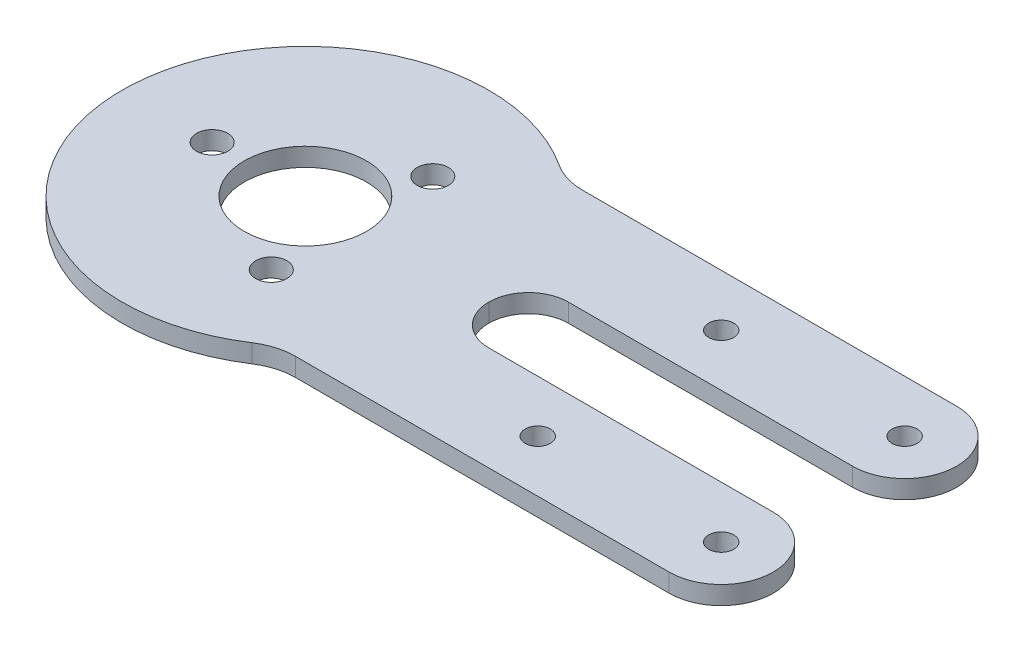
SolidWorks part; units mm, degrees
ref_plane "Front Plane" through (0, 0, 0) normal (0, 0, 1) x (1, 0, 0)
ref_plane "Top Plane" through (0, 0, 0) normal (0, 1, 0) x (1, 0, 0)
ref_plane "Right Plane" through (0, 0, 0) normal (1, 0, 0) x (0, 0, -1)
sketch "Sketch1" plane through (0, 0, 0) normal (0, 1, 0) x (1, 0, 0)
  circle A0 centre (0, 0) radius 30
  dimension "D1" = 60
extrude "Boss-Extrude1" add sketch "Sketch1" along normal blind 3
sketch "Sketch2" plane through (0, 3, 0) normal (0, 1, 0) x (1, 0, 0)
  line L0 (100, 6.5) -> (29.2874, 6.5)
  line L1 (18.6481, 23.5) -> (100, 23.5)
  line L4 (100, 23.5) -> (100, 6.5)
  line L5 (29.2874, -6.5) -> (100, -6.5)
  line L7 (18.6481, -23.5) -> (100, -23.5)
  line L8 (100, -6.5) -> (100, -23.5)
  line L9 (19.2614, 23) -> (100, 23) construction
  line L11 (29.3939, 6) -> (100, 6) construction
  line L12 (100, 23) -> (100, 6) construction
  line L13 (29.3939, -6) -> (100, -6) construction
  line L15 (19.2614, -23) -> (100, -23) construction
  line L16 (100, -6) -> (100, -23) construction
  arc A0 (18.6481, 23.5) -> (29.2874, 6.5) centre (0, 0) cw
  circle A1 centre (0, 0) radius 30 construction
  arc A2 (29.2874, -6.5) -> (18.6481, -23.5) centre (0, 0) cw
  dimension "D1" = 100
  dimension "D2" = 17
  dimension "D3" = 12
  dimension "D4" = 0.5
  dimension "D5" = 0.5
  dimension "D6" = 0
extrude "Boss-Extrude2" add sketch "Sketch2" against normal up to surface (3 mm away) up to face at (0, 0, 30)
sketch "Sketch3" plane through (0, 3, 0) normal (0, 1, 0) x (1, 0, 0)
  line L0 (100, 6.5) -> (100, 23.5) construction
  line L1 (100, -23.5) -> (100, -6.5) construction
  line L2 (53, 15) -> (83, 15) construction
  line L3 (53, 15) -> (53, -15) construction
  line L4 (53, -15) -> (83, -15) construction
  line L5 (83, 15) -> (83, -15) construction
  circle A0 centre (53, 15) radius 2.05
  circle A1 centre (83, 15) radius 2.05
  circle A2 centre (53, -15) radius 2.05
  circle A3 centre (83, -15) radius 2.05
  point P10 (100, 15)
  point P14 (100, -15)
  dimension "D1" = 4.1
  dimension "D2" = 30
  dimension "D3" = 53
extrude "Cut-Extrude1" cut sketch "Sketch3" against normal through all
sketch "Sketch6" plane through (0, 3, 0) normal (0, 1, 0) x (1, 0, 0)
  line L1 (100, 23.5) -> (83, 23.5)
  line L2 (100, 23.5) -> (100, 6.5)
  line L3 (100, 6.5) -> (83, 6.5)
  line L5 (100, -6.5) -> (83, -6.5)
  line L6 (100, -6.5) -> (100, -23.5)
  line L7 (100, -23.5) -> (83, -23.5)
  arc A0 (83, 6.5) -> (83, 23.5) centre (83, 15) ccw
  arc A1 (83, -23.5) -> (83, -6.5) centre (83, -15) ccw
extrude "Cut-Extrude3" cut sketch "Sketch6" against normal through all
fillet "Fillet1" radius 10 2 edges at (18.6481, 1.5, -23.5) (18.6481, 1.5, 23.5)
fillet "Fillet2" radius 6.5 2 edges at (29.2874, 1.5, 6.5) (29.2874, 1.5, -6.5)
sketch "Sketch7" plane through (0, 3, 0) normal (0, 1, 0) x (1, 0, 0)
  circle A0 centre (0, 0) radius 15.25 construction
  circle A1 centre (-15.25, 0) radius 2.55
  dimension "D1" = 30.5
  dimension "D2" = 5.1
extrude "Cut-Extrude4" cut sketch "Sketch7" against normal through all
pattern_circular "CirPattern1" count 3 over 360 about axis through (0, 3, 0) along (0, -1, 0) of "Cut-Extrude4" reverse direction yes
sketch "Sketch8" plane through (0, 3, 0) normal (0, 1, 0) x (1, 0, 0)
  circle A0 centre (0, 0) radius 10
  dimension "D1" = 20
extrude "Cut-Extrude5" cut sketch "Sketch8" against normal through all
